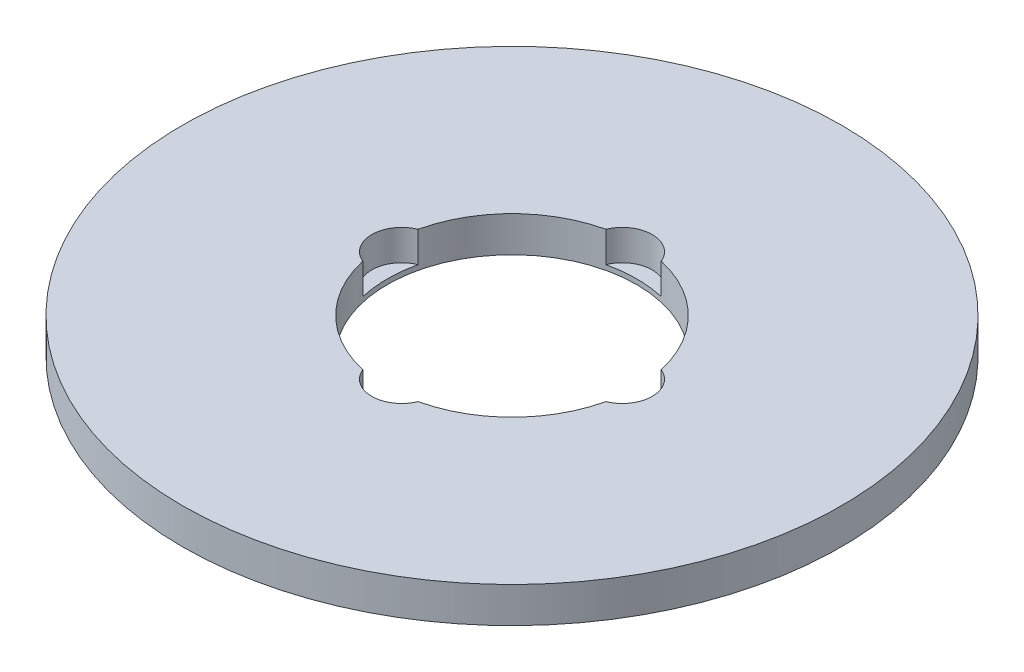
SolidWorks part; units mm, degrees
ref_plane "Front Plane" through (0, 0, 0) normal (0, 0, 1) x (1, 0, 0)
ref_plane "Top Plane" through (0, 0, 0) normal (0, 1, 0) x (1, 0, 0)
ref_plane "Right Plane" through (0, 0, 0) normal (1, 0, 0) x (0, 0, -1)
sketch "Sketch1" plane through (0, 0, 0) normal (0, 1, 0) x (1, 0, 0)
  circle A0 centre (0, 0) radius 92.5
  dimension "FLANGE_OD" = 185
extrude "Boss-Extrude1" add sketch "Sketch1" along normal blind 10
sketch "Sketch2" plane through (0, 0, 0) normal (0, 1, 0) x (1, 0, 0)
  circle A0 centre (0, 0) radius 35
  dimension "BORE_D" = 70
extrude "Cut-Extrude1" cut sketch "Sketch2" along normal through all
sketch "Sketch3" plane through (0, 10, 0) normal (0, 1, 0) x (1, 0, 0)
  circle A0 centre (0, 0) radius 30.974 construction
  circle A1 centre (-30.974, 0) radius 8.377
  dimension "BOLT_D" = 16.7541
  dimension "BOLT_PCD" = 61.948
extrude "Cut-Extrude2" cut sketch "Sketch3" against normal blind 8.6036
pattern_circular "CirPattern1" count 4 over 360 about axis through (0, 0, 0) along (0, 1, 0) of "Cut-Extrude2"
